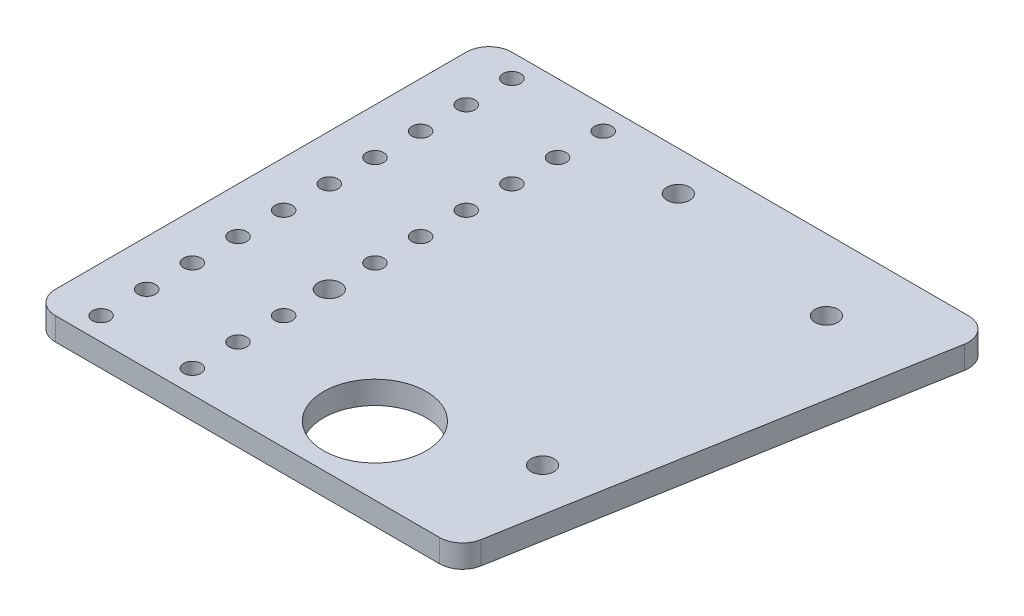
SolidWorks part; units mm, degrees
material "1023 Carbon Steel Sheet (SS)"
ref_plane "Front Plane" through (0, 0, 0) normal (0, 0, 1) x (1, 0, 0)
ref_plane "Top Plane" through (0, 0, 0) normal (0, 1, 0) x (1, 0, 0)
ref_plane "Right Plane" through (0, 0, 0) normal (1, 0, 0) x (0, 0, -1)
sketch "Sketch1" plane through (0, 0, 0) normal (0, 1, 0) x (1, 0, 0)
  line L1 (-64.4036, -58.0213) -> (54.1729, -58.0213)
  line L2 (-64.4036, -58.0213) -> (-64.4036, 68.9787)
  line L3 (-64.4036, 68.9787) -> (76.5664, 68.9787)
  line L4 (54.1729, -58.0213) -> (76.5664, 68.9787)
  line L5 (-64.4036, -58.0213) -> (76.5664, 68.9787) construction
  line L6 (-64.4036, 68.9787) -> (54.1729, -58.0213) construction
  point P0 (0, 0)
  dimension "D1" = 127
  dimension "D2" = 140.97
  dimension "D4" = 80
extrude "Initial Plate" add sketch "Sketch1" along normal blind 6.35
sketch "Sketch3" plane through (0, 6.35, 0) normal (0, 1, 0) x (1, 0, 0)
  line L0 (51.7036, -51.6713) -> (-51.7036, -51.6713) construction
  line L1 (0, 0) -> (0, -51.6713) construction
  line L2 (-64.4036, -58.0213) -> (54.1729, -58.0213) construction
  line L3 (-64.4036, 68.9787) -> (-64.4036, -58.0213) construction
  circle A0 centre (-51.7036, -51.6713) radius 2.413
  circle A1 centre (51.7036, -51.6713) radius 2.413 construction
  circle A2 centre (-26.3036, -51.6713) radius 2.413
  point P4 (0, 0)
  dimension "D1" = 4.826
  dimension "D2" = 6.35
  dimension "D3" = 12.7
  dimension "D4" = 25.4
extrude "Initial Mounting Hole" cut sketch "Sketch3" against normal through all
pattern_linear "Mounting Pattern" count 10 spacing 12.7 along (0, 0, -1) of "Initial Mounting Hole"
sketch "Sketch2" plane through (0, 6.35, 0) normal (0, 1, 0) x (1, 0, 0)
  line L0 (42.7374, 12.2979) -> (-19.7979, 23.3246) construction
  line L1 (-26.3036, -13.5713) -> (-13.2921, 60.2204) construction
  line L2 (36.2317, -24.5979) -> (49.2432, 49.1937) construction
  line L3 (-64.4036, -58.0213) -> (54.1729, -58.0213) construction
  line L4 (-26.7654, 56.1481) -> (-37.2169, 57.991) construction
  line L5 (-16.9839, -8.7666) -> (-27.4353, -6.9237) construction
  line L6 (-13.2921, 60.2204) -> (-0.7851, 58.0151) construction
  line L7 (36.2317, -24.5979) -> (45.7371, -26.274) construction
  circle A1 centre (-26.3036, -13.5713) radius 3.175
  circle A3 centre (49.2432, 49.1937) radius 3.175
  circle A5 centre (-26.3036, -13.5713) radius 6.35 construction
  circle A6 centre (45.7371, -26.274) radius 3.175
  circle A7 centre (-26.3036, -13.5713) radius 2.413 construction
  circle A10 centre (-0.7851, 58.0151) radius 3.175
  circle A11 centre (-0.7851, 58.0151) radius 6.35 construction
  point P4 (1.7785, 19.5201)
  point P7 (-19.7979, 23.3246)
  point P10 (42.7374, 12.2979)
  dimension "D5" = 6.35
  dimension "D2" = 12.7
  dimension "D1" = 63.5
  dimension "D4" = 10
  dimension "D6" = 62.23
  dimension "D8" = 0
  dimension "D3" = 12.7
  dimension "D7" = 9.652
extrude "Bearing Stack Holes" cut sketch "Sketch2" against normal through all
fillet "Fillet1" radius 6.35 4 edges at (76.5664, 3.175, -68.9787) (54.1729, 3.175, 58.0213) (-64.4036, 3.175, 58.0213) (-64.4036, 3.175, -68.9787)
sketch "Sketch4" plane through (0, 6.35, 0) normal (0, 1, 0) x (1, 0, 0)
  circle A0 centre (11.7926, -38.9775) radius 14.2875
  dimension "D1" = 28.575
extrude "Cut-Extrude1" cut sketch "Sketch4" against normal through all
mirror "Mirror1" [suppressed] about plane through (0, 0, 0) normal (1, 0, 0) of bodies 105
delete or keep bodies "Body-Delete/Keep 1" [suppressed] type delete bodies bodies 105
equation "\"D6@Sketch2\"= 2.5in - 0.05in"
